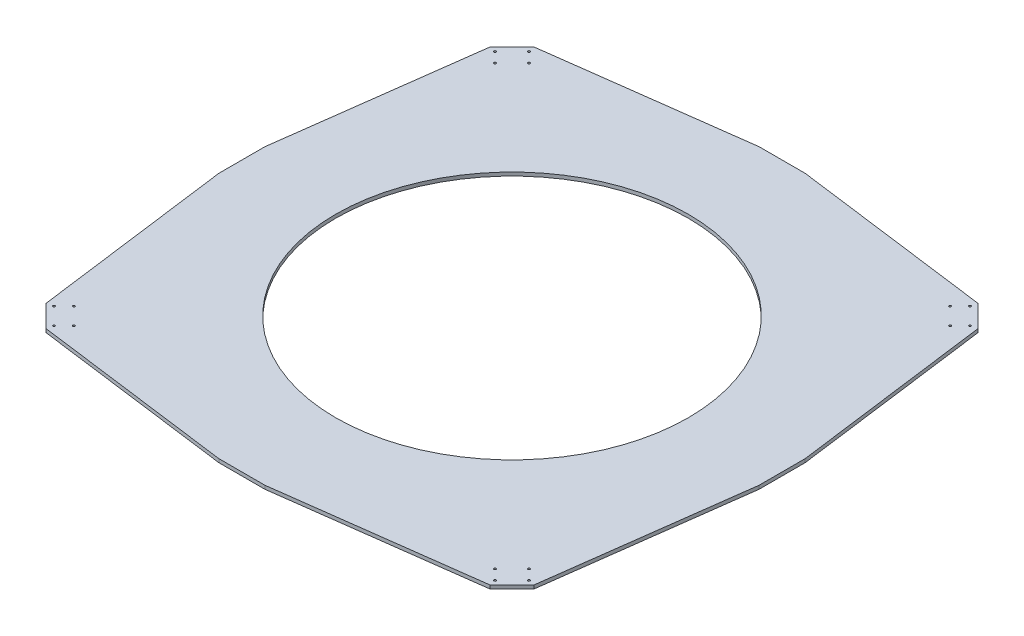
SolidWorks part; units mm, degrees
ref_plane "前视基准面" through (0, 0, 0) normal (0, 0, 1) x (1, 0, 0)
ref_plane "上视基准面" through (0, 0, 0) normal (0, 1, 0) x (1, 0, 0)
ref_plane "右视基准面" through (0, 0, 0) normal (1, 0, 0) x (0, 0, -1)
other "Configuration Table"
sketch "草图1" plane through (0, 0, 0) normal (0, 1, 0) x (1, 0, 0)
  line L0 (-314.9222, 345.9222) -> (-345.9222, 314.9222)
  line L5 (325, -325) -> (-325, 325) construction
  line L6 (325, 325) -> (-325, -325) construction
  line L7 (0, 325) -> (0, -325) construction
  line L8 (-325, 0) -> (325, 0) construction
  line L9 (314.9222, 345.9222) -> (32.7201, 383.0748)
  line L10 (314.9222, 345.9222) -> (345.9222, 314.9222)
  line L12 (-314.9222, 345.9222) -> (-32.7201, 383.0748)
  line L13 (0, 325) -> (0, 399.6983)
  line L14 (-32.7201, 383.0748) -> (32.7201, 383.0748)
  line L15 (314.9222, -345.9222) -> (32.7201, -383.0748)
  line L16 (-32.7201, -383.0748) -> (32.7201, -383.0748)
  line L17 (-314.9222, -345.9222) -> (-32.7201, -383.0748)
  line L18 (-314.9222, -345.9222) -> (-345.9222, -314.9222)
  line L19 (-345.9222, 314.9222) -> (-383.0748, 32.7201)
  line L20 (-383.0748, -32.7201) -> (-383.0748, 32.7201)
  line L21 (-345.9222, -314.9222) -> (-383.0748, -32.7201)
  line L22 (-345.9222, -314.9222) -> (-314.9222, -345.9222)
  line L23 (345.9222, -314.9222) -> (314.9222, -345.9222)
  line L24 (345.9222, -314.9222) -> (383.0748, -32.7201)
  line L25 (383.0748, 32.7201) -> (383.0748, -32.7201)
  line L26 (345.9222, 314.9222) -> (383.0748, 32.7201)
  circle A5 centre (0, 0) radius 250
  circle A6 centre (298.6024, 322.644) radius 1.5
  circle A7 centre (312.7445, 336.7861) radius 1.5
  circle A8 centre (336.7861, 312.7445) radius 1.5
  circle A9 centre (322.644, 298.6024) radius 1.5
  circle A10 centre (298.6024, -322.644) radius 1.5
  circle A11 centre (312.7445, -336.7861) radius 1.5
  circle A12 centre (322.644, -298.6024) radius 1.5
  circle A13 centre (336.7861, -312.7445) radius 1.5
  circle A14 centre (-322.644, -298.6024) radius 1.5
  circle A15 centre (-336.7861, -312.7445) radius 1.5
  circle A16 centre (-298.6024, -322.644) radius 1.5
  circle A17 centre (-312.7445, -336.7861) radius 1.5
  circle A18 centre (-298.6024, 322.644) radius 1.5
  circle A19 centre (-312.7445, 336.7861) radius 1.5
  circle A20 centre (-322.644, 298.6024) radius 1.5
  circle A21 centre (-336.7861, 312.7445) radius 1.5
  point P0 (0, 0)
  point P13 (0, 383.0748)
  point P24 (-330.4222, -330.4222)
  point P75 (0, 0)
  dimension "D8" = 500
  dimension "D5" = 4
  dimension "D1" = 650
  dimension "D2" = 650
  dimension "D3" = 31
  dimension "D4" = 142.5
extrude "凸台-拉伸2" add sketch "草图1" along normal blind 5 contours L26 L10 L9 L14 L12 L0 L19 L20 L21 L18 L17 L16 L15 L23 L24 L25 | A13 L22 | L22 | A13 L18 region at (-172.4069, 0, -353.7562)
sketch "草图2" plane through (0, 5, 0) normal (0, 1, 0) x (1, 0, 0)
  line L0 (0, 0) -> (-330.4222, -330.4222) construction
